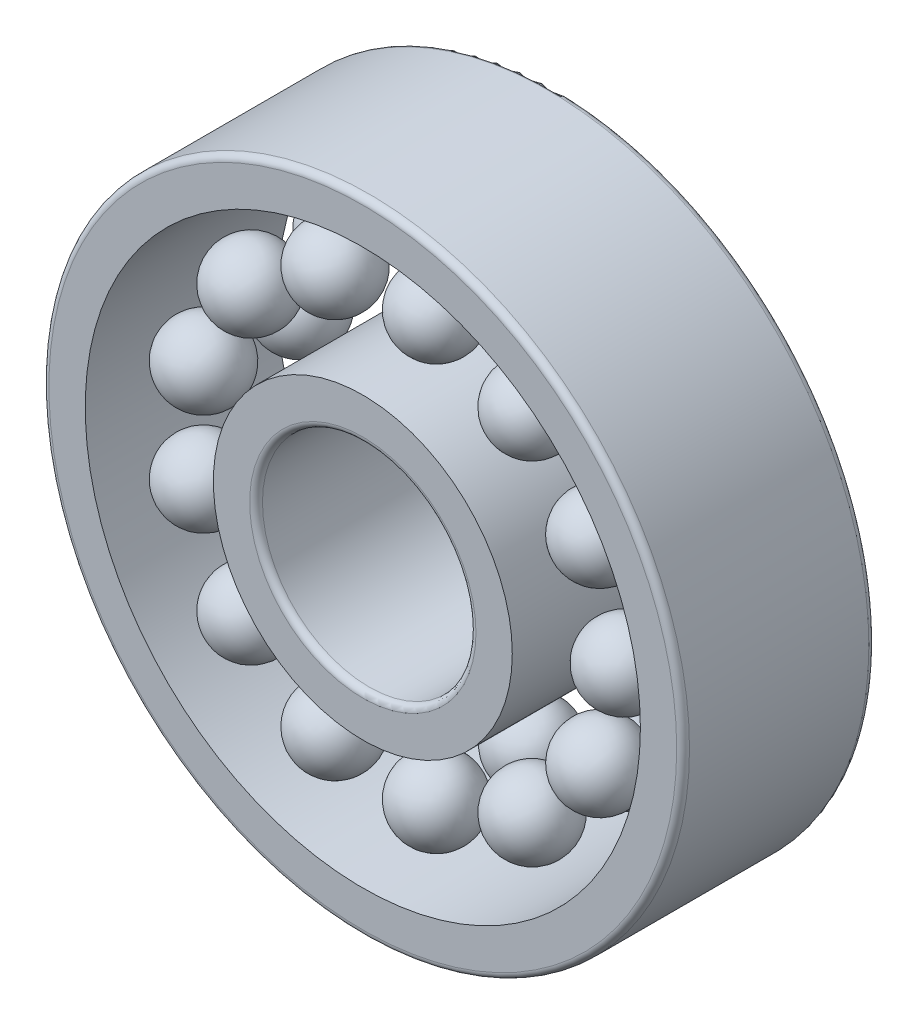
SolidWorks part; units mm, degrees
ref_plane "Front Plane" through (0, 0, 0) normal (0, 0, 1) x (1, 0, 0)
ref_plane "Top Plane" through (0, 0, 0) normal (0, 1, 0) x (1, 0, 0)
ref_plane "Right Plane" through (0, 0, 0) normal (1, 0, 0) x (0, 0, -1)
sketch "S" plane through (0, 0, 0) normal (0, 0, 1) x (1, 0, 0)
  line L0 (-4.5, 0) -> (4.5, 0) construction
  circle A0 centre (0, 0) radius 5 construction
  circle A1 centre (0, 0) radius 15 construction
  circle A2 centre (0, 0) radius 7 construction
  circle A3 centre (0, 0) radius 13 construction
  dimension "ID" = 10
  dimension "OD" = 30
  dimension "IDa" = 14
  dimension "ODa" = 26
  dimension "B" = 9
ref_axis "Z" through (0, 0, -4.95) along (0, 0, 1)
sketch "InnerS" plane through (0, 0, 0) normal (0, 1, 0) x (1, 0, 0)
  line L0 (5, -4.5) -> (7, -4.5)
  line L1 (7, -4.5) -> (7, 4.5)
  line L2 (7, 4.5) -> (5, 4.5)
  line L3 (5, 4.5) -> (5, -4.5)
  line L4 (0, -7.75) -> (0, 7.75) construction
  dimension "r1" = 5
  dimension "r2" = 7
  dimension "z1" = 4.5
  dimension "z2" = 4.5
revolve "InnerRing" add sketch "InnerS" angle 360 about L4
sketch "OuterS" plane through (0, 0, 0) normal (0, 1, 0) x (1, 0, 0)
  line L0 (13, -4.5) -> (15, -4.5)
  line L1 (15, -4.5) -> (15, 4.5)
  line L2 (15, 4.5) -> (13, 4.5)
  line L3 (13, 4.5) -> (13, -4.5)
  line L4 (0, -7.75) -> (0, 7.75) construction
  dimension "z1" = 4.5
  dimension "z2" = 4.5
  dimension "r1" = 13
  dimension "r2" = 15
revolve "OuterRing" add sketch "OuterS" angle 360 about L4
sketch "Ball1S" plane through (0, 0, 0) normal (0, 1, 0) x (1, 0, 0)
  line L0 (8.2, 2.25) -> (11.8, 2.25)
  arc A0 (8.2, 2.25) -> (11.8, 2.25) centre (10, 2.25) ccw
  dimension "r" = 1.8
  dimension "p" = 10
  dimension "z" = 2.25
revolve "Ball1" add sketch "Ball1S" angle 360 about L0
pattern_circular "Ball1sPattern" count 13 over 360 about axis through (0, 0, -4.95) along (0, 0, 1) of bodies 103
sketch "Ball2S" plane through (0, 0, 0) normal (0, 1, 0) x (1, 0, 0)
  line L0 (8.2, -2.25) -> (11.8, -2.25)
  arc A0 (8.2, -2.25) -> (11.8, -2.25) centre (10, -2.25) ccw
  dimension "r" = 1.8
  dimension "p" = 10
  dimension "z" = 2.25
revolve "Ball2" add sketch "Ball2S" angle 360 about L0
pattern_circular "Ball2sPattern" count 13 over 360 about axis through (0, 0, -4.95) along (0, 0, 1) of bodies 116
fillet "F1" radius 0.3 2 edges at (5, 0, -4.5) (5, 0, 4.5)
fillet "F2" radius 0.3 2 edges at (15, 0, -4.5) (15, 0, 4.5)
equation "\"r1@InnerS\" = abs(0.5*\"ID@S\")"
equation "\"r2@InnerS\" = abs(0.5*\"IDa@S\")"
equation "\"z1@InnerS\" = abs(-0.5*\"B@S\")"
equation "\"z2@InnerS\" = abs(0.5*\"B@S\")"
equation "\"r1@OuterS\" = abs(0.5*\"ODa@S\")"
equation "\"r2@OuterS\" = abs(0.5*\"OD@S\")"
equation "\"z1@OuterS\" = abs(-0.5*\"B@S\")"
equation "\"z2@OuterS\" = abs(0.5*\"B@S\")"
equation "\"r@Ball1S\" = abs(0.2*\"B@S\")"
equation "\"p@Ball1S\" = abs(0.25*\"IDa@S\"+0.25*\"ODa@S\")"
equation "\"z@Ball1S\" = abs(0.25*\"B@S\")"
equation "\"N@Ball1sPattern\" = int(2.417*(0.25*\"IDa@S\"+0.25*\"ODa@S\")/(0.2*\"B@S\"))"
equation "\"r@Ball2S\" = abs(0.2*\"B@S\")"
equation "\"p@Ball2S\" = abs(0.25*\"IDa@S\"+0.25*\"ODa@S\")"
equation "\"z@Ball2S\" = abs(-0.25*\"B@S\")"
equation "\"N@Ball2sPattern\" = int(2.417*(0.25*\"IDa@S\"+0.25*\"ODa@S\")/(0.2*\"B@S\"))"
equation "\"r_min@F2\" = \"r_min@F1\""
